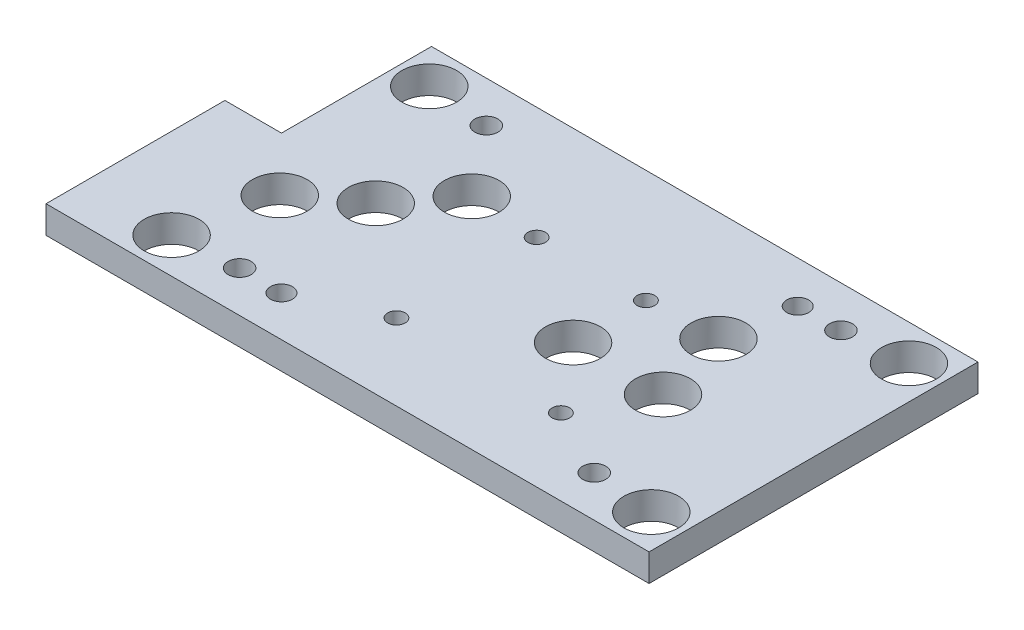
SolidWorks part; units mm, degrees
material "K110"
ref_plane "Front Plane" through (0, 0, 0) normal (0, 0, 1) x (1, 0, 0)
ref_plane "Top Plane" through (0, 0, 0) normal (0, 1, 0) x (1, 0, 0)
ref_plane "Right Plane" through (0, 0, 0) normal (1, 0, 0) x (0, 0, -1)
sketch "Sketch1" plane through (0, 0, 0) normal (0, 1, 0) x (1, 0, 0)
  line L1 (-110, -60) -> (110, -60)
  line L2 (-110, -60) -> (-110, 60)
  line L3 (-110, 60) -> (110, 60)
  line L4 (110, -60) -> (110, 60)
  line L5 (-110, -60) -> (110, 60) construction
  line L6 (-110, 60) -> (110, -60) construction
  point P0 (0, 0)
  dimension "D1" = 120
  dimension "D2" = 220
extrude "Boss-Extrude1" add sketch "Sketch1" against normal blind 10
sketch "Sketch2" plane through (0, 0, 0) normal (0, 1, 0) x (1, 0, 0)
  line L1 (-110, 60) -> (-89.3675, 60)
  line L2 (-110, 60) -> (-110, 5.27)
  line L3 (-110, 5.27) -> (-89.3675, 5.27)
  line L4 (-89.3675, 60) -> (-89.3675, 5.27)
  line L5 (-90, -14.72) -> (-89.3675, 5.27) construction
  line L10 (-70, 0.28) -> (-89.3675, 5.27) construction
  circle A0 centre (-70, 0.28) radius 3.1 construction
  circle A1 centre (-90, -14.72) radius 3.1 construction
  dimension "D1" = 20
extrude "Cut-Extrude1" cut sketch "Sketch2" against normal up to next
sketch "Sketch3" plane through (0, 0, 0) normal (0, 1, 0) x (1, 0, 0)
  circle A0 centre (97.8163, -47) radius 10 construction
  circle A1 centre (-77.1837, -47) radius 10 construction
  circle A2 centre (-70, -14.72) radius 10 construction
  circle A3 centre (-50, 0.28) radius 10 construction
  circle A4 centre (30, -7.72) radius 10 construction
  circle A5 centre (62.8163, -7.72) radius 10 construction
  circle A6 centre (55.3163, 20) radius 10 construction
  circle A7 centre (97.8163, 47) radius 10 construction
  circle A8 centre (-34.6837, 20) radius 10 construction
  circle A9 centre (-77.1837, 47) radius 10 construction
  circle A10 centre (97.8163, -47) radius 10
  circle A11 centre (-77.1837, -47) radius 10
  circle A12 centre (-70, -14.72) radius 10
  circle A13 centre (-50, 0.28) radius 10
  circle A14 centre (30, -7.72) radius 10
  circle A15 centre (62.8163, -7.72) radius 10
  circle A16 centre (55.3163, 20) radius 10
  circle A17 centre (97.8163, 47) radius 10
  circle A18 centre (-34.6837, 20) radius 10
  circle A19 centre (-77.1837, 47) radius 10
extrude "Cut-Extrude2" cut sketch "Sketch3" against normal up to next
hole_wizard "Ø8.0mm Dowel Hole1" positions "Sketch6" profile "Sketch5" hole size "Ø8.0" standard "ISO" end condition through all
sketch "Sketch6" plane through (0, 0, 0) normal (0, 1, 0) x (1, 0, 0)
  point P0 (-38.8675, -45.241)
  point P3 (59.5, 44.7284)
sketch "Sketch5" plane through (-38.8675, 0, 45.241) normal (1, 0, 0) x (0, 0, 1)
  line L0 (0, 0) -> (0, 10)
  line L1 (0, 10) -> (4, 10)
  line L2 (4, 10) -> (4, 0)
  line L5 (4, 0) -> (0, 0)
  line L11 (0, -6.35) -> (0, 107.95) construction
  dimension "Thru Hole Dia." = 8
  dimension "Thru Hole Depth" = 10
hole_wizard "M8 Clearance Hole1" positions "Sketch9" profile "Sketch8" hole size "M8" standard "ISO" end condition through all
sketch "Sketch9" plane through (0, 0, 0) normal (0, 1, 0) x (1, 0, 0)
  point P0 (-54.3675, 45)
  point P3 (75, 45)
  point P6 (75, -45)
  point P9 (-54.3675, -45)
sketch "Sketch8" plane through (-54.3675, 0, -45) normal (1, 0, 0) x (0, 0, 1)
  line L0 (0, 0) -> (0, 10)
  line L1 (0, 10) -> (4.2, 10)
  line L2 (4.2, 10) -> (4.2, 0)
  line L5 (4.2, 0) -> (0, 0)
  line L11 (0, -6.35) -> (0, 107.95) construction
  dimension "Thru Hole Dia." = 8.4
  dimension "Thru Hole Depth" = 10
hole_wizard "M6 Clearance Hole1" positions "Sketch12" profile "Sketch11" hole size "M6" standard "ISO" end condition through all
sketch "Sketch12" plane through (0, 0, 0) normal (0, 1, 0) x (1, 0, 0)
  point P0 (30, 18.86)
  point P3 (-9.875, 18.86)
  point P6 (-10, -32.16)
  point P9 (50, -32.16)
sketch "Sketch11" plane through (30, 0, -18.86) normal (1, 0, 0) x (0, 0, 1)
  line L0 (0, 0) -> (0, 10)
  line L1 (0, 10) -> (3.2, 10)
  line L2 (3.2, 10) -> (3.2, 0)
  line L5 (3.2, 0) -> (0, 0)
  line L11 (0, -6.35) -> (0, 107.95) construction
  dimension "Thru Hole Dia." = 6.4
  dimension "Thru Hole Depth" = 10
